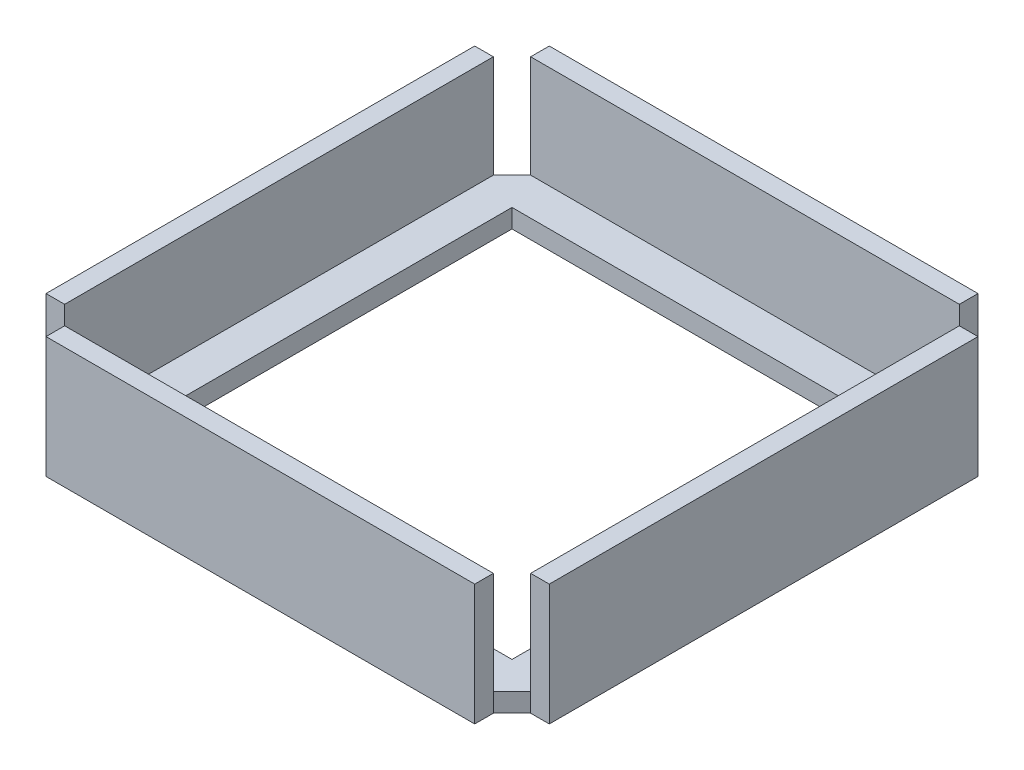
SolidWorks part; units mm, degrees
ref_plane "Front Plane" through (0, 0, 0) normal (0, 0, 1) x (1, 0, 0)
ref_plane "Top Plane" through (0, 0, 0) normal (0, 1, 0) x (1, 0, 0)
ref_plane "Right Plane" through (0, 0, 0) normal (1, 0, 0) x (0, 0, -1)
sketch "Sketch1" plane through (0, 0, 0) normal (0, 1, 0) x (1, 0, 0)
  line L0 (-42, 31) -> (-42, 9.4579) construction
  line L1 (-42, 33) -> (4, 33)
  line L2 (-40, 27) -> (2, 27)
  line L3 (-40, 27) -> (-40, -15)
  line L4 (-40, -15) -> (2, -15)
  line L5 (2, 27) -> (2, -15)
  line L6 (-46, 29) -> (-46, -17)
  line L7 (-42, -21) -> (4, -21)
  line L8 (8, 29) -> (8, -17)
  line L9 (-46, 29) -> (-35.2489, 29) construction
  line L10 (4, 31) -> (4, 23.7598) construction
  line L11 (-44, -17) -> (-37.8676, -17) construction
  line L12 (-42, 31) -> (-44, 29)
  line L13 (-42, 33) -> (-42, 31)
  line L14 (-44, 29) -> (-46, 29)
  line L15 (4, 33) -> (4, 31)
  line L16 (6, 29) -> (8, 29)
  line L17 (8, -17) -> (6, -17)
  line L18 (-46, -17) -> (-44, -17)
  line L19 (4, -21) -> (4, -19)
  line L20 (-42, -21) -> (-42, -19)
  line L21 (-44, -17) -> (-42, -19)
  line L22 (4, -19) -> (-42, -19)
  line L23 (4, -19) -> (6, -17)
  line L24 (6, -17) -> (6, 29)
  line L25 (6, 29) -> (4, 31)
  line L26 (4, 31) -> (-42, 31)
  line L27 (-44, 29) -> (-44, -17)
extrude "Boss-Extrude3" add sketch "Sketch1" along normal blind 2 contours L12 L27 L21 L22 L23 L24 L25 L26 L2 L5 L4 L3 region at (-19, 0, -30.2929)
extrude "Boss-Extrude6" add sketch "Sketch1<26>" along normal blind 13 contours L19 L22 L20 L7 | L26 L15 L1 L13 | L24 L17 L8 L16 | L27 L14 L6 L18 region at (-19, 0, -32) region at (-45, 0, -6) region at (7, 0, -6) region at (-19, 0, 20)
sketch "Sketch1<26>" plane through (0, 0, 0) normal (0, 1, 0) x (1, 0, 0) same geometry as "Sketch1"
